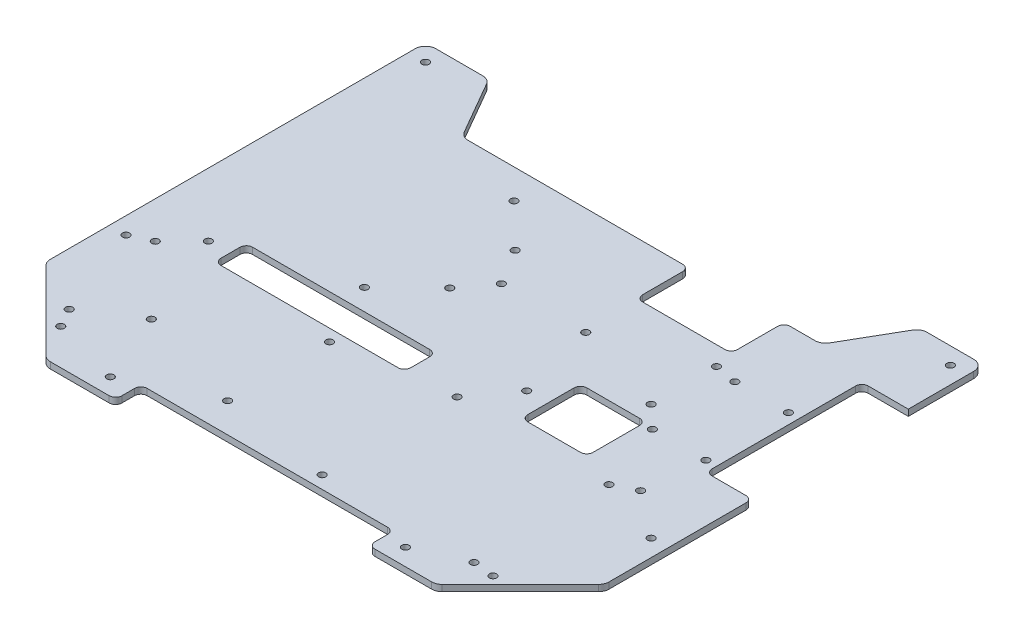
SolidWorks part; units mm, degrees
material "Acier non allié"
ref_plane "Front" through (0, 0, 0) normal (0, 0, 1) x (1, 0, 0)
ref_plane "Top" through (0, 0, 0) normal (0, 1, 0) x (1, 0, 0)
ref_plane "Right" through (0, 0, 0) normal (1, 0, 0) x (0, 0, -1)
sketch "Esquisse1" plane through (0, 0, 0) normal (0, 1, 0) x (1, 0, 0)
  line L0 (0, 0) -> (0, 190) construction
  line L1 (-92.5, 0) -> (92.5, 0)
  line L2 (92.5, 0) -> (132.5, 40)
  line L3 (132.5, 40) -> (132.5, 220)
  line L4 (132.5, 220) -> (102.5, 220)
  line L5 (102.5, 220) -> (85.1795, 190)
  line L6 (85.1795, 190) -> (-85.1795, 190)
  line L7 (-102.5, 220) -> (-85.1795, 190)
  line L8 (-132.5, 220) -> (-102.5, 220)
  line L9 (-132.5, 40) -> (-132.5, 220)
  line L10 (-92.5, 0) -> (-132.5, 40)
  dimension "D1" = 132.5
  dimension "D2" = 220
  dimension "D3" = 60
  dimension "D4" = 30
  dimension "D5" = 40
  dimension "D6" = 40
  dimension "D7" = 30
extrude "Boss.-Extru.1" add sketch "Esquisse1" along normal blind 3
fillet "Congé1" radius 5 10 edges at (92.5, 1.5, 0) (132.5, 1.5, -40) (132.5, 1.5, -220) (102.5, 1.5, -220) (85.1795, 1.5, -190) (-85.1795, 1.5, -190) (-102.5, 1.5, -220) (-132.5, 1.5, -220) (-92.5, 1.5, 0) (-132.5, 1.5, -40)
sketch "Esquisse2" plane through (0, 3, 0) normal (0, 1, 0) x (1, 0, 0)
  line L0 (0, 0) -> (0, 294.1173) construction
  line L2 (-90.4289, 0) -> (90.4289, 0) construction
  circle A0 centre (70, 8) radius 1
  circle A1 centre (124.5, 70) radius 1
  circle A2 centre (124.5, 212) radius 1
  circle A3 centre (-124.5, 212) radius 1
  circle A4 centre (-124.5, 70) radius 1
  circle A5 centre (-70, 8) radius 1
  dimension "D2" = 2
  dimension "D6" = 2
  dimension "D9" = 2
  dimension "D1" = 70
  dimension "D3" = 8
  dimension "D4" = 124.5
  dimension "D5" = 70
  dimension "D7" = 124.5
  dimension "D8" = 212
extrude "Enlèv. mat.-Extru.1" cut sketch "Esquisse2" against normal blind 3
hole_wizard "Dégagement M31" positions "Esquisse3" profile "Esquisse4" hole size "M3" standard "ISO" end condition through all
sketch "Esquisse3" plane through (0, 3, 0) normal (0, 1, 0) x (1, 0, 0)
  point P0 (70, 8)
  point P3 (-70, 8)
  point P6 (-124.5, 70)
  point P9 (-124.5, 212)
  point P12 (124.5, 212)
  point P15 (124.5, 70)
sketch "Esquisse4" plane through (70, 3, -8) normal (1, 0, 0) x (0, 0, 1)
  line L0 (0, 0) -> (0, 3)
  line L1 (0, 3) -> (1.7, 3)
  line L2 (1.7, 3) -> (1.7, 0)
  line L5 (1.7, 0) -> (0, 0)
  line L11 (0, -6.35) -> (0, 107.95) construction
  dimension "Diamètre du perçage jusqu'au prochain" = 3.4
  dimension "Profondeur du perçage jusqu'au prochain" = 3
sketch "Esquisse5" plane through (0, 3, 0) normal (0, 1, 0) x (1, 0, 0)
  line L0 (82.2927, 190) -> (-82.2927, 190) construction
  line L1 (67.5, 190) -> (22.5, 190)
  line L2 (67.5, 190) -> (67.5, 165)
  line L3 (67.5, 165) -> (22.5, 165)
  line L4 (22.5, 190) -> (22.5, 165)
  line L5 (132.5, 42.0711) -> (132.5, 215) construction
  line L6 (132.5, 184) -> (110.5, 184)
  line L7 (132.5, 184) -> (132.5, 110)
  line L8 (132.5, 110) -> (110.5, 110)
  line L9 (110.5, 184) -> (110.5, 110)
  line L10 (127.5, 220) -> (105.3868, 220) construction
  dimension "D1" = 25
  dimension "D2" = 65
  dimension "D3" = 110
  dimension "D4" = 36
  dimension "D5" = 110
  dimension "D6" = 22
extrude "Enlèv. mat.-Extru.2" cut sketch "Esquisse5" against normal through all
fillet "Congé2" radius 3 7 edges at (132.5, 1.5, -110) (110.5, 1.5, -110) (110.5, 1.5, -184) (67.5, 1.5, -190) (67.5, 1.5, -165) (22.5, 1.5, -165) (22.5, 1.5, -190)
sketch "Esquisse6" plane through (0, 3, 0) normal (0, 1, 0) x (1, 0, 0)
  line L0 (110.5, 140.5) -> (-167.6757, 140.5) construction
  line L1 (110.5, 181) -> (110.5, 113) construction
  line L2 (-90.4289, 0) -> (90.4289, 0) construction
  line L3 (110.5, 181) -> (110.5, 113) construction
  circle A0 centre (69.5, 156) radius 1
  circle A1 centre (-26, 156) radius 1
  circle A2 centre (-46.5, 176) radius 1
  circle A3 centre (69.5, 125) radius 1
  circle A4 centre (-26, 125) radius 1
  circle A5 centre (-46.5, 105) radius 1
  dimension "D4" = 2
  dimension "D6" = 2
  dimension "D10" = 2
  dimension "D1" = 140.5
  dimension "D2" = 41
  dimension "D3" = 15.5
  dimension "D5" = 136.5
  dimension "D7" = 15.5
  dimension "D8" = 35.5
  dimension "D9" = 157
extrude "Enlèv. mat.-Extru.3" cut sketch "Esquisse6" against normal through all
hole_wizard "Dégagement M32" positions "Esquisse7" profile "Esquisse8" hole size "M3" standard "ISO"
sketch "Esquisse7" plane through (0, 3, 0) normal (0, 1, 0) x (1, 0, 0)
  point P0 (-46.5, 105)
  point P3 (-26, 125)
  point P6 (-26, 156)
  point P9 (-46.5, 176)
  point P12 (69.5, 156)
  point P15 (69.5, 125)
sketch "Esquisse8" plane through (-46.5, 3, -105) normal (1, 0, 0) x (0, 0, 1)
  line L0 (0, 0) -> (0, 11.0215)
  line L1 (0, 11.0215) -> (1.7, 10)
  line L2 (1.7, 10) -> (1.7, 0)
  line L5 (1.7, 0) -> (0, 0)
  line L10 (0, 11.0215) -> (-1.7, 10) construction
  line L11 (0, -6.35) -> (0, 107.95) construction
  dimension "Diamètre du perçage" = 3.4
  dimension "Profondeur du perçage" = 10
  dimension "Angle de pointe" = 118
sketch "Esquisse9" plane through (0, 3, 0) normal (0, 1, 0) x (1, 0, 0)
  line L0 (132.5, 42.0711) -> (132.5, 107) construction
  line L1 (-90.4289, 0) -> (90.4289, 0) construction
  line L2 (-107.5, 26) -> (-32.37, 26) construction
  line L7 (20.5, 18) -> (20.5, 82) construction
  line L8 (25.5, 165) -> (64.5, 165) construction
  line L9 (24.5, 139) -> (-15.5, 139) construction
  line L10 (110.5, 181) -> (110.5, 113) construction
  line L11 (113.5, 110) -> (129.5, 110) construction
  line L13 (-32.37, 26) -> (-32.37, 74.3362) construction
  line L14 (-32.37, 74.3362) -> (-115, 74.3362) construction
  line L15 (-132.5, 215) -> (-132.5, 42.0711) construction
  circle A0 centre (105.5, 115) radius 1
  circle A3 centre (105.5, 154.12) radius 1
  circle A10 centre (20.5, 82) radius 1
  circle A11 centre (92.5, 82) radius 1
  circle A12 centre (20.5, 18) radius 1
  circle A13 centre (92.5, 18) radius 1
  circle A14 centre (-15.5, 139) radius 1
  circle A15 centre (24.5, 139) radius 1
  circle A16 centre (34.5, 101) radius 1
  circle A17 centre (80.1, 115) radius 1
  circle A18 centre (80.1, 154.12) radius 1
  circle A19 centre (-107.5, 26) radius 1.5
  circle A21 centre (-32.37, 26) radius 1.5
  circle A22 centre (-32.37, 74.3362) radius 1.5
  circle A23 centre (-115, 74.3362) radius 1.5
  circle A24 centre (-83.99, 41.44) radius 1.5
  dimension "D2" = 2
  dimension "D4" = 2
  dimension "D21" = 2
  dimension "D22" = 2
  dimension "D23" = 2
  dimension "D24" = 2
  dimension "D32" = 2
  dimension "D33" = 2
  dimension "D34" = 2
  dimension "D11" = 2
  dimension "D12" = 2
  dimension "D17" = 3
  dimension "D18" = 3
  dimension "D19" = 3
  dimension "D36" = 3
  dimension "D42" = 3
  dimension "D5" = 27
  dimension "25" = 27
  dimension "D10" = 39.12
  dimension "D25" = 72
  dimension "D26" = 72
  dimension "D27" = 64
  dimension "D28" = 64
  dimension "D30" = 18
  dimension "D31" = 18
  dimension "D37" = 40
  dimension "D39" = 10
  dimension "D7" = 5
  dimension "D8" = 25.4
  dimension "D9" = 25.4
  dimension "D40" = 39.12
  dimension "D38" = 76
  dimension "D6" = 38
  dimension "D35" = 26
  dimension "D14" = 40
  dimension "D13" = 75.13
  dimension "D15" = 82.63
  dimension "D16" = 48.3362
  dimension "D20" = 26
  dimension "D29" = 25
  dimension "D41" = 23.51
  dimension "D43" = 15.44
extrude "Enlèv. mat.-Extru.4" cut sketch "Esquisse9" against normal through all
hole_wizard "Dégagement M33" positions "Esquisse10" profile "Esquisse11" hole size "M3" standard "ISO"
sketch "Esquisse10" plane through (0, 3, 0) normal (0, 1, 0) x (1, 0, 0)
  point P3 (105.5, 115)
  point P9 (105.5, 154.12)
  point P14 (80.1, 154.12)
  point P17 (80.1, 115)
sketch "Esquisse11" plane through (105.5, 3, -115) normal (1, 0, 0) x (0, 0, 1)
  line L0 (0, 0) -> (0, 11.0215)
  line L1 (0, 11.0215) -> (1.7, 10)
  line L2 (1.7, 10) -> (1.7, 0)
  line L5 (1.7, 0) -> (0, 0)
  line L10 (0, 11.0215) -> (-1.7, 10) construction
  line L11 (0, -6.35) -> (0, 107.95) construction
  dimension "Diamètre du perçage" = 3.4
  dimension "Profondeur du perçage" = 10
  dimension "Angle de pointe" = 118
sketch "Esquisse12" plane through (0, 3, 0) normal (0, 1, 0) x (1, 0, 0)
  line L2 (-90.4289, 0) -> (90.4289, 0) construction
  line L3 (102.5, 17) -> (-102.5, 17) construction
  line L4 (102.5, 17) -> (102.5, 87) construction
  line L5 (102.5, 87) -> (-102.5, 87) construction
  line L6 (-102.5, 17) -> (-102.5, 87) construction
  line L7 (132.5, 42.0711) -> (132.5, 107) construction
  circle A4 centre (-102.5, 87) radius 1
  circle A5 centre (102.5, 87) radius 1
  circle A6 centre (102.5, 17) radius 1
  circle A7 centre (-102.5, 17) radius 1
  point P6 (102.5, 52)
  dimension "D5" = 2
  dimension "D6" = 2
  dimension "D7" = 2
  dimension "D8" = 2
  dimension "D1" = 70
  dimension "D2" = 205
  dimension "D3" = 17
  dimension "D4" = 30
extrude "Enlèv. mat.-Extru.5" cut sketch "Esquisse12" against normal through all and the other way through all
hole_wizard "Dégagement M34" positions "Esquisse13" profile "Esquisse14" hole size "M3" standard "ISO"
sketch "Esquisse13" plane through (0, 3, 0) normal (0, 1, 0) x (1, 0, 0)
  point P16 (20.5, 18)
  point P19 (92.5, 18)
  point P22 (20.5, 82)
  point P25 (92.5, 82)
  point P29 (34.5, 101)
  point P32 (24.5, 139)
  point P35 (-15.5, 139)
  point P38 (-115, 74.3362)
  point P41 (-32.37, 74.3362)
  point P44 (-107.5, 26)
  point P47 (-32.37, 26)
  point P50 (-83.99, 41.44)
sketch "Esquisse14" plane through (20.5, 3, -18) normal (1, 0, 0) x (0, 0, 1)
  line L0 (0, 0) -> (0, 11.0215)
  line L1 (0, 11.0215) -> (1.7, 10)
  line L2 (1.7, 10) -> (1.7, 0)
  line L5 (1.7, 0) -> (0, 0)
  line L10 (0, 11.0215) -> (-1.7, 10) construction
  line L11 (0, -6.35) -> (0, 107.95) construction
  dimension "Diamètre du perçage" = 3.4
  dimension "Profondeur du perçage" = 10
  dimension "Angle de pointe" = 118
hole_wizard "Dégagement M35" positions "Esquisse15" profile "Esquisse16" hole size "M3" standard "ISO"
sketch "Esquisse15" plane through (0, 3, 0) normal (0, 1, 0) x (1, 0, 0)
  point P0 (-102.5, 17)
  point P3 (-102.5, 87)
  point P6 (102.5, 87)
  point P9 (102.5, 17)
sketch "Esquisse16" plane through (-102.5, 3, -17) normal (1, 0, 0) x (0, 0, 1)
  line L0 (0, 0) -> (0, 11.0215)
  line L1 (0, 11.0215) -> (1.7, 10)
  line L2 (1.7, 10) -> (1.7, 0)
  line L5 (1.7, 0) -> (0, 0)
  line L10 (0, 11.0215) -> (-1.7, 10) construction
  line L11 (0, -6.35) -> (0, 107.95) construction
  dimension "Diamètre du perçage" = 3.4
  dimension "Profondeur du perçage" = 10
  dimension "Angle de pointe" = 118
sketch "Esquisse17" plane through (0, 3, 0) normal (0, 1, 0) x (1, 0, 0)
  line L0 (-90.4289, 0) -> (90.4289, 0) construction
  line L1 (-92.5, 95) -> (-2.5, 95)
  line L2 (-92.5, 95) -> (-92.5, 80)
  line L3 (-92.5, 80) -> (-2.5, 80)
  line L4 (-2.5, 95) -> (-2.5, 80)
  line L5 (-132.5, 215) -> (-132.5, 42.0711) construction
  line L6 (132.5, 42.0711) -> (132.5, 107) construction
  line L7 (44.5, 116.5) -> (75.5, 116.5)
  line L8 (44.5, 116.5) -> (44.5, 88.5)
  line L9 (44.5, 88.5) -> (75.5, 88.5)
  line L10 (75.5, 116.5) -> (75.5, 88.5)
  line L11 (82.2927, 190) -> (70.5, 190) construction
  line L13 (-59.5, 12) -> (60.5, 12)
  line L14 (-59.5, 12) -> (-59.5, 0)
  line L15 (-59.5, 0) -> (60.5, 0)
  line L16 (60.5, 12) -> (60.5, 0)
  dimension "D1" = 90
  dimension "D2" = 15
  dimension "D3" = 80
  dimension "D4" = 40
  dimension "D5" = 31
  dimension "D6" = 28
  dimension "D7" = 57
  dimension "D8" = 73.5
  dimension "D9" = 12
  dimension "D11" = 120
  dimension "D12" = 72
extrude "Enlèv. mat.-Extru.6" cut sketch "Esquisse17" against normal up to surface (3 mm away) up to face at (-102.5, 0, -15.3)
fillet "Congé3" radius 3 12 edges at (60.5, 1.5, 0) (60.5, 1.5, -12) (-59.5, 1.5, -12) (-59.5, 1.5, 0) (44.5, 1.5, -116.5) (75.5, 1.5, -116.5) (75.5, 1.5, -88.5) (44.5, 1.5, -88.5) (-92.5, 1.5, -80) (-2.5, 1.5, -80) (-2.5, 1.5, -95) (-92.5, 1.5, -95)
equation "\"WIDTH\"= 300mm'Total width of the robot"
equation "\"LENGTH\"= 220mm'Total length of the robot"
equation "\"CUT_DEPTH\"= 45mm'Depth of the cut on the edges of the plate"
equation "\"Plate_th\"= 3mm'Thickness of the plate"
equation "\"D1\"= \"Plate_th\""
equation "\"D5@Esquisse9\"=\"25@Esquisse9\""
